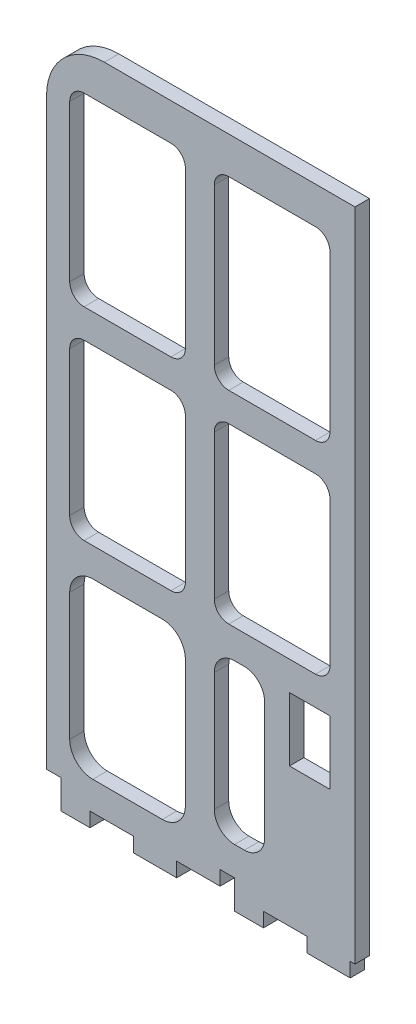
SolidWorks part; units mm, degrees
material "Balsa"
ref_plane "Front Plane" through (0, 0, 0) normal (0, 0, 1) x (1, 0, 0)
ref_plane "Top Plane" through (0, 0, 0) normal (0, 1, 0) x (1, 0, 0)
ref_plane "Right Plane" through (0, 0, 0) normal (1, 0, 0) x (0, 0, -1)
sketch "Sketch1" plane through (0, 0, 0) normal (0, 0, 1) x (1, 0, 0)
  line L1 (135.4577, 0) -> (135.4577, 287.9852)
  line L2 (135.4577, 287.9852) -> (25.4, 287.9852)
  line L4 (0, 0) -> (0, -6.35)
  line L6 (0, 0) -> (0, -6.35)
  line L7 (0, -6.35) -> (19.05, -6.35)
  line L8 (19.05, 0) -> (19.05, -6.35)
  line L10 (38.1, 0) -> (38.1, -6.35)
  line L11 (38.1, -6.35) -> (57.15, -6.35)
  line L12 (57.15, 0) -> (57.15, -6.35)
  line L14 (76.2, 0) -> (76.2, -6.35)
  line L15 (76.2, -6.35) -> (95.25, -6.35)
  line L16 (95.25, 0) -> (95.25, -6.35)
  line L18 (114.3, 0) -> (114.3, -6.35)
  line L19 (114.3, -6.35) -> (133.35, -6.35)
  line L20 (133.35, 0) -> (133.35, -6.35)
  line L25 (19.05, 0) -> (38.1, 0)
  line L26 (57.15, 0) -> (76.2, 0)
  line L27 (95.25, 0) -> (114.3, 0)
  line L28 (133.35, 0) -> (135.4577, 0)
  line L30 (0, 262.5852) -> (0, 0)
  line L31 (25.4, 287.9852) -> (135.4577, 287.9852)
  line L32 (19.05, 0) -> (38.1, 0)
  line L33 (38.1, -6.35) -> (57.15, -6.35)
  line L34 (57.15, 0) -> (76.2, 0)
  arc A0 (25.4, 287.9852) -> (0, 262.5852) centre (25.4, 262.5852) ccw
  point P8 (0, 287.9852)
  point P11 (135.4577, 287.9852)
  dimension "D4" = 6.35
  dimension "D5" = 19.05
  dimension "D1" = 135.4577
  dimension "D2" = 287.9852
  dimension "D3" = 135.4577
  dimension "D6" = 6.35
  dimension "D7" = 19.05
  dimension "D8" = 19.05
  dimension "D9" = 19.05
  dimension "D10" = 19.05
  dimension "D11" = 6.35
  dimension "D12" = 19.05
  dimension "D13" = 19.05
  dimension "D14" = 6.35
  dimension "D15" = 6.35
  dimension "D16" = 0
  dimension "D17" = 262.5852
  dimension "D21" = 6.35
  dimension "D22" = 6.35
  dimension "D23" = 6.35
extrude "Boss-Extrude1" add sketch "Sketch1" along normal blind 6.35 contours L2 A0 L30 L4 L7 L8 L25 L10 L11 L12 L26 L14 L15 L16 L27 L18 L19 L20 L1 region at (67.9342, 141.6966, 0)
sketch "Sketch2" plane through (0, 0, 6.35) normal (0, 0, 1) x (1, 0, 0)
  line L38 (73.66, 22.86) -> (73.66, 78.74)
  line L39 (20.32, 12.7) -> (50.8, 12.7)
  line L40 (73.66, 196.85) -> (73.66, 265.43)
  line L41 (80.01, 190.5) -> (118.11, 190.5)
  line L42 (124.46, 196.85) -> (124.46, 265.43)
  line L43 (80.01, 271.78) -> (118.11, 271.78)
  line L45 (10.16, 196.85) -> (10.16, 265.43)
  line L46 (16.51, 190.5) -> (54.61, 190.5)
  line L47 (60.96, 196.85) -> (60.96, 265.43)
  line L48 (16.51, 271.78) -> (54.61, 271.78)
  line L49 (73.66, 107.95) -> (73.66, 171.45)
  line L50 (80.01, 101.6) -> (118.11, 101.6)
  line L51 (124.46, 107.95) -> (124.46, 171.45)
  line L52 (80.01, 177.8) -> (118.11, 177.8)
  line L53 (10.16, 107.95) -> (10.16, 171.45)
  line L54 (16.51, 101.6) -> (54.61, 101.6)
  line L55 (60.96, 107.95) -> (60.96, 171.45)
  line L56 (16.51, 177.8) -> (54.61, 177.8)
  line L68 (10.16, 22.86) -> (10.16, 78.74)
  line L69 (20.32, 88.9) -> (50.8, 88.9)
  line L70 (60.96, 22.86) -> (60.96, 78.74)
  line L71 (83.82, 12.7) -> (114.3, 12.7)
  line L72 (124.46, 22.86) -> (124.46, 78.74)
  line L73 (83.82, 88.9) -> (114.3, 88.9)
  line L104 (19.05, -38.1) -> (44.45, -38.1) [skipped]
  line L105 (137.16, 19.05) -> (137.16, 82.55) [skipped]
  line L106 (146.05, 12.7) -> (171.45, 12.7) [skipped]
  line L107 (187.96, 19.05) -> (187.96, 82.55) [skipped]
  line L108 (146.05, 88.9) -> (171.45, 88.9) [skipped]
  line L109 (137.16, -44.45) -> (137.16, 19.05) [skipped]
  line L110 (146.05, -50.8) -> (171.45, -50.8) [skipped]
  line L111 (187.96, -44.45) -> (187.96, 19.05) [skipped]
  line L112 (146.05, 25.4) -> (171.45, 25.4) [skipped]
  line L113 (137.16, -103.373) -> (137.16, -49.027) [skipped]
  line L114 (150.627, -114.3) -> (166.873, -114.3) [skipped]
  line L115 (187.96, -103.373) -> (187.96, -49.027) [skipped]
  line L116 (150.627, -38.1) -> (166.873, -38.1) [skipped]
  line L117 (73.66, -97.4702) -> (73.66, -54.9298) [skipped]
  line L118 (124.46, -97.4702) -> (124.46, -54.9298) [skipped]
  line L119 (93.0298, -114.3) -> (97.4702, -114.3) [skipped]
  line L120 (93.0298, -38.1) -> (97.4702, -38.1) [skipped]
  line L121 (10.16, -105.3232) -> (10.16, -47.0768) [skipped]
  line L122 (37.2067, -114.3) -> (48.1202, -114.3) [skipped]
  line L123 (60.96, -105.3232) -> (60.96, -58.7589) [skipped]
  line L124 (19.05, 25.4) -> (44.45, 25.4) [skipped]
  line L125 (60.96, -50.8) -> (60.96, 25.4) [skipped]
  line L126 (19.05, -50.8) -> (44.45, -50.8) [skipped]
  line L127 (10.16, -50.8) -> (10.16, 25.4) [skipped]
  line L128 (124.46, -69.3053) -> (124.46, 6.8947) [skipped]
  line L129 (73.66, -50.8) -> (73.66, 25.4) [skipped]
  line L130 (94.7053, 25.4) -> (103.4599, 25.4) [skipped]
  line L131 (94.7053, -50.8) -> (103.4599, -50.8) [skipped]
  arc A24 (73.66, 78.74) -> (83.82, 88.9) centre (83.82, 78.74) cw
  arc A25 (124.46, 78.74) -> (114.3, 88.9) centre (114.3, 78.74) ccw
  arc A26 (114.3, 12.7) -> (124.46, 22.86) centre (114.3, 22.86) ccw
  arc A27 (73.66, 22.86) -> (83.82, 12.7) centre (83.82, 22.86) ccw
  arc A28 (50.8, 12.7) -> (60.96, 22.86) centre (50.8, 22.86) ccw
  arc A29 (50.8, 88.9) -> (60.96, 78.74) centre (50.8, 78.74) cw
  arc A30 (10.16, 78.74) -> (20.32, 88.9) centre (20.32, 78.74) cw
  arc A31 (20.32, 12.7) -> (10.16, 22.86) centre (20.32, 22.86) cw
  arc A57 (10.16, 196.85) -> (16.51, 190.5) centre (16.51, 196.85) ccw
  arc A58 (10.16, 265.43) -> (16.51, 271.78) centre (16.51, 265.43) cw
  arc A59 (60.96, 265.43) -> (54.61, 271.78) centre (54.61, 265.43) ccw
  arc A60 (54.61, 190.5) -> (60.96, 196.85) centre (54.61, 196.85) ccw
  arc A61 (73.66, 196.85) -> (80.01, 190.5) centre (80.01, 196.85) ccw
  arc A62 (73.66, 265.43) -> (80.01, 271.78) centre (80.01, 265.43) cw
  arc A63 (124.46, 265.43) -> (118.11, 271.78) centre (118.11, 265.43) ccw
  arc A64 (118.11, 190.5) -> (124.46, 196.85) centre (118.11, 196.85) ccw
  arc A65 (10.16, 107.95) -> (16.51, 101.6) centre (16.51, 107.95) ccw
  arc A66 (10.16, 171.45) -> (16.51, 177.8) centre (16.51, 171.45) cw
  arc A67 (60.96, 171.45) -> (54.61, 177.8) centre (54.61, 171.45) ccw
  arc A68 (54.61, 101.6) -> (60.96, 107.95) centre (54.61, 107.95) ccw
  arc A69 (73.66, 107.95) -> (80.01, 101.6) centre (80.01, 107.95) ccw
  arc A70 (73.66, 171.45) -> (80.01, 177.8) centre (80.01, 171.45) cw
  arc A71 (124.46, 171.45) -> (118.11, 177.8) centre (118.11, 171.45) ccw
  arc A72 (118.11, 101.6) -> (124.46, 107.95) centre (118.11, 107.95) ccw
  point P88 (60.96, 12.7)
  point P93 (10.16, 88.9)
  point P96 (10.16, 12.7)
  dimension "D7" = 81.28
  dimension "D12" = 76.2
  dimension "D11" = 50.8
  dimension "D1" = 76.2
  dimension "D2" = 50.8
  dimension "D3" = 3
  dimension "D4" = 3
  dimension "D5" = 10.16
  dimension "D6" = 12.7
  dimension "D8" = 12.7
  dimension "D9" = 81.28
  dimension "D10" = 50.8
  dimension "D13" = 76.2
  dimension "D14" = 50.8
  dimension "D15" = 50.8
  dimension "D16" = 12.7
  dimension "D17" = 12.7
  dimension "D18" = 0
  dimension "D19" = 0
  dimension "D20" = 12.7
  dimension "D21" = 12.7
  dimension "D22" = 12.7
  dimension "D23" = 12.7
extrude "Cut-Extrude1" cut sketch "Sketch2" against normal through all
sketch "Sketch3" plane through (0, 0, 6.35) normal (0, 0, 1) x (1, 0, 0)
  line L1 (0, -6.35) -> (6.35, -6.35)
  line L2 (0, -6.35) -> (0, 6.35)
  line L3 (0, 6.35) -> (6.35, 6.35)
  line L4 (6.35, -6.35) -> (6.35, 6.35)
  line L5 (76.2, -6.35) -> (82.55, -6.35)
  line L6 (76.2, -6.35) -> (76.2, 6.35)
  line L7 (76.2, 6.35) -> (82.55, 6.35)
  line L8 (82.55, -6.35) -> (82.55, 6.35)
  dimension "D1" = 6.35
  dimension "D2" = 12.7
  dimension "D3" = 6.35
  dimension "D4" = 12.7
extrude "Cut-Extrude2" cut sketch "Sketch3" against normal through all
sketch "Sketch4" plane through (0, 0, 6.35) normal (0, 0, 1) x (1, 0, 0)
  line L5 (69.1558, 89.874) -> (128.0503, 89.874)
  line L6 (69.1558, 89.874) -> (69.1558, 9.4409)
  line L7 (69.1558, 9.4409) -> (128.0503, 9.4409)
  line L8 (128.0503, 89.874) -> (128.0503, 9.4409)
  dimension "D1" = 80.433
extrude "Boss-Extrude3" add sketch "Sketch4" against normal up to surface (6.35 mm away) from surface contours L8 L7 L6 L5 up to face at (99.06, 50.8, 0) starting at face at (66.7676, 35.5833, 6.35)
ref_plane "Plane1" through (50.8, 88.9, 0) normal (-1, 0, 0) x (0, 0, 1)
sketch "Sketch6" plane through (0, 0, 0) normal (0, 0, -1) x (-1, 0, 0)
  line L1 (-124.46, 88.9) -> (-106.68, 88.9)
  line L2 (-124.46, 88.9) -> (-124.46, 60.96)
  line L3 (-124.46, 60.96) -> (-106.68, 60.96)
  line L4 (-106.68, 88.9) -> (-106.68, 60.96)
  dimension "D1" = 17.78
  dimension "D2" = 27.94
extrude "Cut-Extrude3" cut sketch "Sketch6" against normal through all
sketch "Sketch7" plane through (0, 0, 6.35) normal (0, 0, 1) x (1, 0, 0)
  line L0 (50.8, 88.9) -> (20.32, 88.9) construction
  line L1 (82.55, 88.9) -> (86.868, 88.9)
  line L2 (73.66, 80.01) -> (73.66, 27.94)
  line L3 (82.55, 19.05) -> (86.868, 19.05)
  line L4 (95.758, 80.01) -> (95.758, 27.94)
  line L5 (73.66, 171.45) -> (73.66, 107.95) construction
  line L6 (82.55, -6.35) -> (95.25, -6.35) construction
  line L7 (106.68, 60.96) -> (106.68, 88.9) construction
  arc A0 (73.66, 27.94) -> (82.55, 19.05) centre (82.55, 27.94) ccw
  arc A1 (86.868, 19.05) -> (95.758, 27.94) centre (86.868, 27.94) ccw
  arc A2 (86.868, 88.9) -> (95.758, 80.01) centre (86.868, 80.01) cw
  arc A3 (82.55, 88.9) -> (73.66, 80.01) centre (82.55, 80.01) ccw
  dimension "D2" = 8.89
  dimension "D1" = 10.922
  dimension "D3" = 25.4
extrude "Cut-Extrude4" cut sketch "Sketch7" against normal up to surface (6.35 mm away) up to face at (115.57, 74.93, 0)
